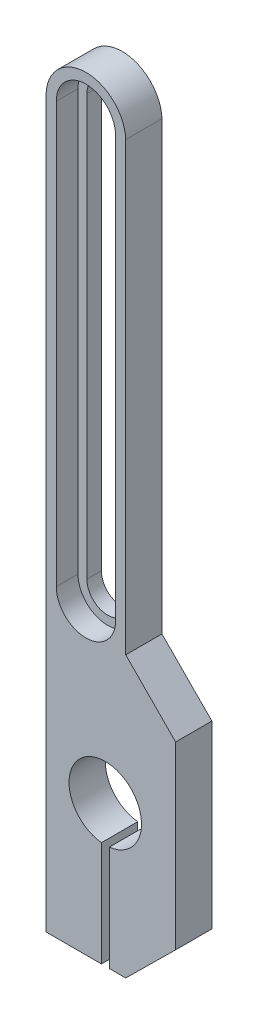
SolidWorks part; units mm, degrees
ref_plane "Front Plane" through (0, 0, 0) normal (0, 0, 1) x (1, 0, 0)
ref_plane "Top Plane" through (0, 0, 0) normal (0, 1, 0) x (1, 0, 0)
ref_plane "Right Plane" through (0, 0, 0) normal (1, 0, 0) x (0, 0, -1)
sketch "Sketch1" plane through (0, 0, 0) normal (0, 0, 1) x (1, 0, 0)
  line L0 (-10.1683, -74.5401) -> (-10.1683, 125.8735)
  line L1 (-10.1683, -74.5401) -> (11.8083, -74.5401)
  line L2 (11.8083, -74.5401) -> (25.5847, -60.9277)
  line L3 (25.5847, -60.9277) -> (25.5847, -11.2343)
  line L4 (25.5847, -11.2343) -> (11.8083, 2.7081)
  line L5 (11.8083, 2.7081) -> (11.8083, 125.8735)
  line L6 (0.82, 125.4599) -> (0.82, 9.4303) construction
  line L7 (6.5602, 125.4599) -> (6.5602, 9.4303)
  line L8 (-4.9201, 125.4599) -> (-4.9201, 9.4303)
  arc A0 (-10.1683, 125.8735) -> (11.8083, 125.8735) centre (0.82, 125.4599) cw
  arc A1 (6.5602, 125.4599) -> (-4.9201, 125.4599) centre (0.82, 125.4599) ccw
  arc A2 (-4.9201, 9.4303) -> (6.5602, 9.4303) centre (0.82, 9.4303) ccw
  point P8 (0.82, 67.4451)
  dimension "D1" = 200
extrude "Boss-Extrude1" add sketch "Sketch1" along normal blind 10
sketch "Sketch2" plane through (0, 0, 10) normal (0, 0, 1) x (1, 0, 0)
  line L0 (0.82, 125.4599) -> (0.82, 9.4303) construction
  line L3 (9.0029, 125.4599) -> (9.0029, 9.4303)
  line L4 (-7.3629, 125.4599) -> (-7.3629, 9.4303)
  arc A3 (9.0029, 125.4599) -> (-7.3629, 125.4599) centre (0.82, 125.4599) ccw
  arc A4 (-7.3629, 9.4303) -> (9.0029, 9.4303) centre (0.82, 9.4303) ccw
  point P3 (0.82, 67.4451)
extrude "Cut-Extrude1" cut sketch "Sketch2" against normal blind 6
sketch "Sketch3" plane through (0, 0, 10) normal (0, 0, 1) x (1, 0, 0)
  circle A0 centre (6.1525, -35.5904) radius 10
  point P2 (6.1525, -35.5904)
extrude "Cut-Extrude2" cut sketch "Sketch3" against normal blind 100
sketch "Sketch4" plane through (0, 0, 10) normal (0, 0, 1) x (1, 0, 0)
  line L1 (5.1048, -26.2085) -> (7.2728, -26.2085)
  line L2 (5.1048, -26.2085) -> (5.1048, -78.6251)
  line L3 (5.1048, -78.6251) -> (7.2728, -78.6251)
  line L4 (7.2728, -26.2085) -> (7.2728, -78.6251)
extrude "Cut-Extrude3" cut sketch "Sketch4" against normal blind 100
